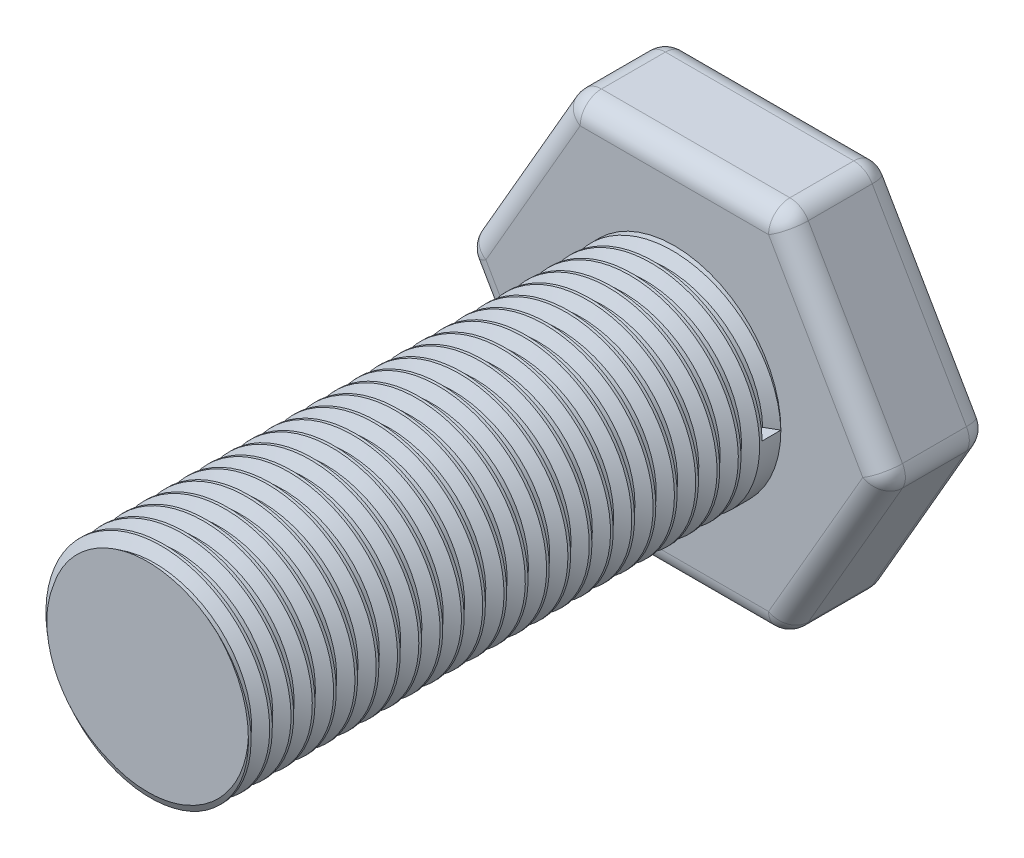
SolidWorks part; units mm, degrees
ref_plane "Plan de face" through (0, 0, 0) normal (0, 0, 1) x (1, 0, 0)
ref_plane "Plan de dessus" through (0, 0, 0) normal (0, 1, 0) x (1, 0, 0)
ref_plane "Plan de droite" through (0, 0, 0) normal (1, 0, 0) x (0, 0, -1)
sketch "Esquisse2" plane through (0, 0, 0) normal (0, 0, 1) x (1, 0, 0)
  line L1 (5, 8.6603) -> (-5, 8.6603)
  line L2 (-5, 8.6603) -> (-10, 0)
  line L3 (-10, 0) -> (-5, -8.6603)
  line L4 (-5, -8.6603) -> (5, -8.6603)
  line L5 (5, -8.6603) -> (10, 0)
  line L6 (10, 0) -> (5, 8.6603)
  circle A0 centre (0, 0) radius 8.6603 construction
  dimension "D1" = 20
extrude "Boss.-Extru.1" add sketch "Esquisse2" along normal blind 5
sketch "Esquisse3" plane through (0, 0, 5) normal (0, 0, 1) x (1, 0, 0)
  circle A0 centre (0, 0) radius 5
  dimension "D1" = 10
extrude "Boss.-Extru.2" add sketch "Esquisse3" along normal blind 25
thread "Filetage1" pitch 1 method cut profile "Profil de filetage2" start angle 0, offset 0, length 0, pitch 1, diameter 10
ref_plane "Plan2" through (5, 0, 5) normal (0, -1, 0) x (1, 0, 0)
sketch "Profil de filetage2" plane through (5, 0, 5) normal (0, -1, 0) x (1, 0, 0)
  line L0 (0, 0) -> (0, 1) construction
  line L11 (0, 0) -> (0, 0.875)
  line L12 (0, 0.875) -> (-0.5413, 0.5625)
  line L13 (-0.5413, 0.5625) -> (-0.5413, 0.3125)
  line L15 (-0.5413, 0.3125) -> (0, 0)
  line L17 (-0.5413, 0.4375) -> (0, 0.4375) construction
  point P2 (0, 0)
  dimension "Pitch" = 1
  dimension "Profile_Angle" = 60
  dimension "Profile_Land" = 0.25
  dimension "Profile_Height" = 0.5413
fillet "Congé1" radius 1 18 edges at (-7.5, 4.3301, 5) (-7.5, 4.3301, 0) (-10, 0, 2.5) (-7.5, -4.3301, 5) (-7.5, -4.3301, 0) (7.5, 4.3301, 5) (7.5, 4.3301, 0) (5, 8.6603, 2.5) (0, 8.6603, 5) (-5, 8.6603, 2.5) (0, 8.6603, 0) (-5, -8.6603, 2.5) (0, -8.6603, 5) (0, -8.6603, 0) (5, -8.6603, 2.5) (7.5, -4.3301, 5) (10, 0, 2.5) (7.5, -4.3301, 0)
